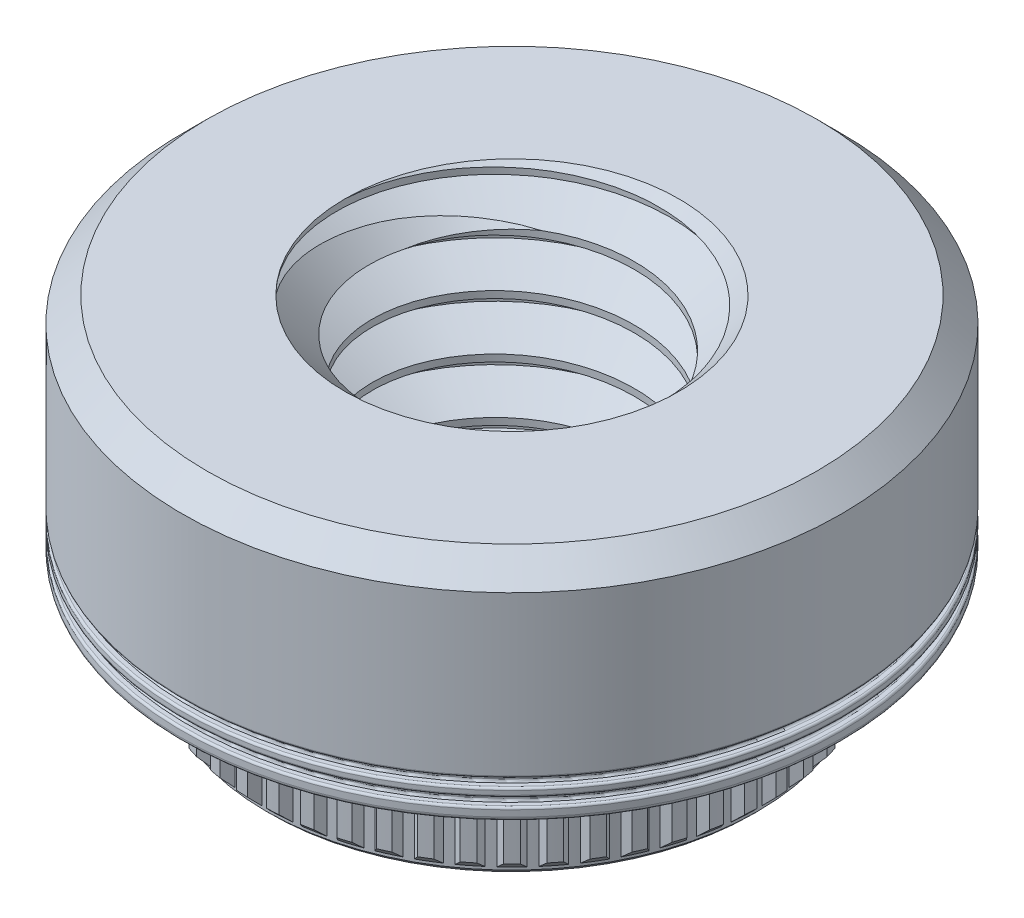
SolidWorks part; units mm, degrees
material "Alloy Steel"
ref_plane "Front Plane" through (0, 0, 0) normal (0, 0, 1) x (1, 0, 0)
ref_plane "Top Plane" through (0, 0, 0) normal (0, 1, 0) x (1, 0, 0)
ref_plane "Right Plane" through (0, 0, 0) normal (1, 0, 0) x (0, 0, -1)
sketch "Sketch1" plane through (0, 0, 0) normal (0, 0, 1) x (1, 0, 0)
  line L0 (0, -2.3749) -> (0, 2.3749) construction
  line L1 (-4.7625, 2.3749) -> (4.7625, 2.3749) construction
  line L2 (-3.683, -2.3749) -> (3.683, -2.3749) construction
  line L3 (-2.4989, 2.3253) -> (-2.4989, 3.119) construction
  line L4 (-2.4989, 3.119) -> (-1.8115, 2.7222) construction
  line L5 (-1.8115, 2.7222) -> (-2.4989, 2.3253) construction
  line L6 (-2.4989, 2.7222) -> (-2.413, 2.7222) construction
  line L7 (-2.413, 2.7222) -> (-1.8974, 2.7222) construction
  line L8 (-1.8974, 2.7222) -> (-1.8115, 2.7222) construction
  line L9 (-1.8974, 2.6726) -> (-1.8974, 2.7718) construction
  line L10 (-2.413, 2.3749) -> (-2.413, 3.0694) construction
  line L11 (-2.456, 2.3501) -> (-2.456, 3.0942) construction
  point P4 (0, 0)
  point P7 (0, 2.3749)
  point P10 (0, -0.8509)
  point P13 (0, -2.3749)
  point P14 (-2.413, 2.3749)
  point P15 (2.413, 2.3749)
  point P24 (-1.8974, 2.7222)
  point P28 (-2.413, 2.7222)
  point P31 (-2.456, 2.7222)
  dimension "Head OD" = 9.525
  dimension "Head Height" = 3.2258
  dimension "For Minimum Panel Thickness" = 1.524
  dimension "OD2" = 7.366
  dimension "Thread Pitch" = 0.7937
  dimension "D1" = 0.0992
  dimension "Thread Size" = 4.826
sketch "Sketch2" plane through (0, 0, 0) normal (0, 0, 1) x (1, 0, 0)
  line L0 (0, -2.3749) -> (0, 2.3749) construction
  line L1 (-3.4544, -2.3749) -> (3.4544, -2.3749) construction
  line L2 (-3.4544, -2.3749) -> (-3.4544, -0.8509)
  line L3 (-3.4544, -0.8509) -> (3.4544, -0.8509) construction
  line L4 (3.4544, -2.3749) -> (3.4544, -0.8509)
  line L5 (-3.4544, -2.3749) -> (3.4544, -0.8509) construction
  line L6 (-3.4544, -0.8509) -> (3.4544, -2.3749) construction
  line L7 (-3.683, -2.3749) -> (3.683, -2.3749) construction
  point P0 (0, -1.6129)
  dimension "Drill Bit Decimal Size Equivalent" = 6.9088
sketch "Sketch3" plane through (0, 0, 0) normal (0, 0, 1) x (1, 0, 0)
  line L1 (-2.413, 2.3749) -> (-2.413, -2.3749)
  line L3 (-3.683, -2.3749) -> (3.683, -2.3749) construction
  line L4 (-4.7625, 2.3749) -> (4.7625, 2.3749) construction
  line L5 (-3.683, -2.1387) -> (-3.5496, -2.272)
  line L6 (-3.5496, -2.272) -> (-3.5496, -2.3749) construction
  line L7 (-3.5496, -2.3749) -> (-2.413, -2.3749) construction
  line L8 (-2.413, 2.3749) -> (-4.4053, 2.3749)
  line L9 (-4.4053, 2.3749) -> (-4.7625, 2.0177)
  line L10 (-4.7625, 2.0177) -> (-4.7625, -0.2763)
  line L11 (-3.683, -2.1387) -> (-3.683, -1.1366) construction
  line L12 (-3.683, -1.1366) -> (-3.4544, -1.1366) construction
  line L13 (-3.4544, -0.8509) -> (3.4544, -0.8509) construction
  line L14 (-3.4544, -2.3749) -> (-3.4544, -0.8509) construction
  line L15 (-3.4544, -1.0652) -> (-3.4544, -0.9223)
  line L16 (-3.5258, -0.8509) -> (-4.702, -0.8509)
  line L17 (-4.7323, -0.6694) -> (-4.6718, -0.6694)
  line L18 (-4.6415, -0.6392) -> (-4.6415, -0.5787)
  line L19 (-4.6718, -0.5485) -> (-4.7323, -0.5485)
  line L20 (-4.7323, -0.4275) -> (-4.6718, -0.4275)
  line L21 (-4.6415, -0.3973) -> (-4.6415, -0.3368)
  line L22 (-4.6718, -0.3065) -> (-4.7323, -0.3065)
  line L23 (-4.7625, -0.6997) -> (-4.7625, -0.7904)
  line L24 (-4.7625, -0.4578) -> (-4.7625, -0.5182)
  line L25 (0, -2.3749) -> (0, 2.3749) construction
  line L26 (0, -2.3749) -> (0, 2.3749) construction
  line L27 (-3.683, -1.27) -> (-3.5497, -1.1366)
  line L28 (-3.683, -2.1387) -> (-3.683, -1.27)
  line L29 (-3.5497, -1.1366) -> (-3.5258, -1.1366)
  line L30 (3.683, -2.1387) -> (-3.683, -2.1387) construction
  line L31 (-3.5496, -2.3106) -> (-3.4854, -2.3749)
  line L32 (-3.4854, -2.3749) -> (-2.413, -2.3749)
  line L33 (-3.5496, -2.3106) -> (-3.5496, -2.272)
  arc A0 (-4.702, -0.8509) -> (-4.7625, -0.7904) centre (-4.702, -0.7904) cw
  arc A1 (-3.5258, -1.1366) -> (-3.4544, -1.0652) centre (-3.5258, -1.0652) ccw
  arc A2 (-3.4544, -0.9223) -> (-3.5258, -0.8509) centre (-3.5258, -0.9223) ccw
  arc A3 (-4.6415, -0.3368) -> (-4.6718, -0.3065) centre (-4.6718, -0.3368) ccw
  arc A4 (-4.6718, -0.4275) -> (-4.6415, -0.3973) centre (-4.6718, -0.3973) ccw
  arc A5 (-4.6415, -0.5787) -> (-4.6718, -0.5485) centre (-4.6718, -0.5787) ccw
  arc A6 (-4.6718, -0.6694) -> (-4.6415, -0.6392) centre (-4.6718, -0.6392) ccw
  arc A7 (-4.7323, -0.3065) -> (-4.7625, -0.2763) centre (-4.7323, -0.2763) cw
  arc A8 (-4.7323, -0.4275) -> (-4.7625, -0.4578) centre (-4.7323, -0.4578) ccw
  arc A9 (-4.7323, -0.5485) -> (-4.7625, -0.5182) centre (-4.7323, -0.5182) cw
  arc A10 (-4.7323, -0.6694) -> (-4.7625, -0.6997) centre (-4.7323, -0.6997) ccw
  point P44 (-3.4544, -0.8509)
  point P46 (0, -2.1387)
  point P60 (-4.7625, -0.4275)
  point P65 (-4.7625, -0.6694)
  dimension "D4" = 0.0605
  dimension "D1" = 0.0714
  dimension "D10" = 0.0302
  dimension "D2" = 45
  dimension "D3" = 0.2858
  dimension "D5" = 0.121
  dimension "D6" = 3.683
  dimension "D7" = 0.2362
  dimension "D8" = 0.1029
  dimension "D9" = 0.1333
  dimension "D11" = 0.0643
  dimension "D12" = 0.3572
  dimension "D13" = 0.0605
revolve "Revolve1" add sketch "Sketch3" angle 360 about L26
sketch "Sketch8" plane through (0, 0, 0) normal (0, 0, 1) x (1, 0, 0)
  line L0 (2.413, -2.3749) -> (2.413, 2.3749) construction
  line L1 (-2.413, 2.3749) -> (-2.413, -2.3749) construction
  line L2 (2.413, -2.3749) -> (2.413, 2.3749)
  line L3 (-2.413, 2.3749) -> (-2.413, -2.3749)
  line L4 (-3.683, -1.27) -> (-3.683, -2.1387) construction
  line L5 (3.683, -2.1387) -> (3.683, -1.27) construction
  line L6 (-3.683, -1.27) -> (-3.683, -2.1387)
  line L7 (3.683, -2.1387) -> (3.683, -1.27)
  point P4 (2.413, 1.1843)
  dimension "D1" = 1.1906
sketch "Sketch4" plane through (0, 2.3749, 0) normal (0, 1, 0) x (1, 0, 0)
  circle A0 centre (0, 0) radius 2.413
curve "Helix/Spiral1" pitch 0.7937 height 5.5435 radius 2.413 centre (0, 2.3749, 0) axis (0, -1, 0) start towards (-1, 0, 0)
sketch "Sketch5" plane through (0, 0, 0) normal (0, 0, 1) x (1, 0, 0)
  line L0 (-2.456, 2.3501) -> (-2.456, 3.0942)
  line L1 (-2.456, 3.0942) -> (-1.8974, 2.7718)
  line L2 (-1.8974, 2.7718) -> (-1.8974, 2.6726)
  line L3 (-1.8974, 2.6726) -> (-2.456, 2.3501)
sweep "Sweep1" add profiles "Sketch5" path "Helix/Spiral1"
sketch "Sketch6" plane through (0, 0, 0) normal (0, 0, 1) x (1, 0, 0)
  line L1 (-2.4989, 3.4365) -> (-2.4989, 2.3749)
  line L4 (-1.8115, 1.7734) -> (-1.8115, 3.4365)
  line L5 (-1.8115, 3.4365) -> (-2.4989, 3.4365)
  line L7 (0, 0) -> (-4.7625, 0) construction
  line L13 (0, -2.3749) -> (0, 2.3749) construction
  line L14 (0, -2.3749) -> (0, 2.3749) construction
  line L15 (-4.7625, 2.0177) -> (-4.7625, -0.2763) construction
  line L21 (-2.413, 2.3749) -> (-1.8115, 1.7734)
  line L26 (-4.7625, 2.3749) -> (4.7625, 2.3749) construction
  line L27 (-2.4989, 2.3749) -> (-2.413, 2.3749)
  line L28 (-2.4989, 2.3253) -> (-2.4989, 3.119) construction
  line L29 (-2.4989, -2.3749) -> (-2.413, -2.3749)
  line L30 (-2.413, -2.3749) -> (-1.8115, -1.7734)
  line L31 (-1.8115, -3.4365) -> (-2.4989, -3.4365)
  line L32 (-1.8115, -1.7734) -> (-1.8115, -3.4365)
  line L33 (-2.4989, -3.4365) -> (-2.4989, -2.3749)
  point P16 (0, 0)
  dimension "D1" = 45
  dimension "D2" = 0.3175
  dimension "D3" = 45
revolve "Cut-Revolve1" cut sketch "Sketch6" angle 360 about L14
sketch "Sketch7" plane through (0, -2.3749, 0) normal (0, -1, 0) x (1, 0, 0)
  line L1 (0, 0) -> (0, 3.4431) construction
  line L2 (-0.2, 3.7896) -> (0.2, 3.7896) construction
  line L3 (0.2, 3.7896) -> (0, 3.4431) construction
  line L4 (0, 3.4431) -> (-0.2, 3.7896) construction
  line L5 (0, 3.7896) -> (0, 3.683) construction
  line L6 (0, 3.683) -> (0, 3.5496) construction
  line L7 (0, 3.5496) -> (0, 3.4431) construction
  line L8 (-0.0615, 3.5496) -> (0.0615, 3.5496) construction
  line L9 (-0.1385, 3.683) -> (0.1385, 3.683)
  line L10 (0, 0) -> (0.1385, 3.683) construction
  line L12 (0.0612, 3.5491) -> (0.1385, 3.683)
  line L13 (-0.1385, 3.683) -> (-0.0612, 3.5491)
  line L14 (-0.1385, 3.683) -> (0, 0) construction
  circle A1 centre (0, 0) radius 3.683 construction
  arc A2 (0.0612, 3.5491) -> (-0.0612, 3.5491) centre (0, 0) ccw
  circle A5 centre (0, 0) radius 3.5496 construction
  point P17 (0, 3.5496)
  point P21 (0, 3.683)
  dimension "D1" = 0.4001
  dimension "D2" = 0.123
  dimension "D3" = 4.307
extrude "Cut-Extrude1" cut sketch "Sketch7" against normal up to vertex (1.2383 mm away) contours L8 L12 L9 region at (0, -2.3749, 3.6248) up to point (-3.683, -1.1366, 0)
pattern_circular "CirPattern1" count 52 over 360 about axis through (0, -2.1387, 0) along (0, -1, 0) of "Cut-Extrude1"
equation "\"D1@Sketch1\"=\"Thread Pitch@Sketch1\"/8"
equation "\"D3@Sketch3\"=\"For Minimum Panel Thickness@Sketch1\"*(3/16)"
equation "\"D4@Sketch3\"=\"Head Height@Sketch1\"*0.01875"
equation "\"D5@Sketch3\"=\"D4@Sketch3\"*2"
equation "\"D7@Sketch3\"=\"For Minimum Panel Thickness@Sketch1\"*0.155"
equation "\"D8@Sketch3\"=\"For Minimum Panel Thickness@Sketch1\"*0.0675"
equation "\"D3@Helix/Spiral1\"=\"Head Height@Sketch1\"+\"For Minimum Panel Thickness@Sketch1\"+\"Thread Pitch@Sketch1\""
equation "\"D4@Helix/Spiral1\"=\"Thread Pitch@Sketch1\""
equation "\"D1@Sketch3\"=\"D3@Sketch3\"*0.25"
equation "\"D1@Sketch7\"=\"D9@Sketch3\"*3"
equation "\"D1@Sketch8\"=\"Thread Pitch@Sketch1\"*1.5"
equation "\"D1@CirPattern1\"= int ( ( 360 / \"D3@Sketch7\" ) * 0.625 )"
equation "\"D10@Sketch3\"=\"D5@Sketch3\"*0.25"
equation "\"D11@Sketch3\"=\"D8@Sketch3\"*0.625"
equation "\"D12@Sketch3\"=\"Head OD@Sketch1\"*0.0375"
equation "\"D13@Sketch3\"=\"D5@Sketch3\"*0.5"
